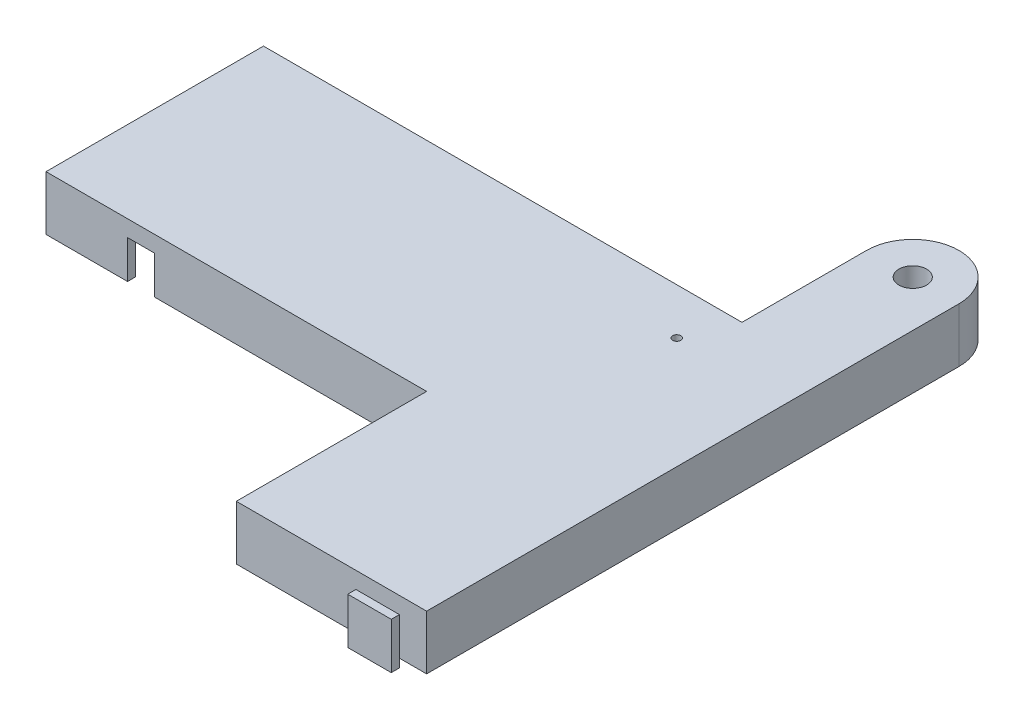
SolidWorks part; units mm, degrees
ref_plane "Front Plane" through (0, 0, 0) normal (0, 0, 1) x (1, 0, 0)
ref_plane "Top Plane" through (0, 0, 0) normal (0, 1, 0) x (1, 0, 0)
ref_plane "Right Plane" through (0, 0, 0) normal (1, 0, 0) x (0, 0, -1)
sketch "CornerSketch1" plane through (0, 0, 0) normal (0, 1, 0) x (1, 0, 0)
  line L0 (210, -70) -> (140, -70)
  line L2 (0, 80) -> (176, 80)
  line L5 (140, -70) -> (140, 0)
  line L6 (140, 0) -> (0, 0)
  line L7 (0, 80) -> (0, 0)
  line L8 (176, 125.825) -> (176, 80)
  line L10 (210, 125.825) -> (210, -70)
  arc A0 (210, 125.825) -> (176, 125.825) centre (193, 125.825) ccw
  dimension "D3" = 34
  dimension "D4" = 70
  dimension "D6" = 45.825
  dimension "D2" = 210
  dimension "D5" = 150
  dimension "D7" = 80
extrude "CornerBoss-Extrude1" add sketch "CornerSketch1" along normal blind 20
shell "Shell1" thickness 3 removed face at (131.5, 0, -36.0813)
sketch "PadSketch2" plane through (0, 17, 0) normal (0, -1, 0) x (1, 0, 0)
  line L0 (210, 70) -> (210, -125.825) construction
  line L1 (176, -80) -> (0, -80) construction
  circle A0 centre (193, -125.825) radius 12
  circle A1 centre (169, -63) radius 5
  dimension "D2" = 10
  dimension "D1" = 24
  dimension "D3" = 41
  dimension "D4" = 17
extrude "PadBoss-Extrude2" add sketch "PadSketch2" along normal blind 10
sketch "StepperRodHoleSketch3" plane through (0, 7, 0) normal (0, -1, 0) x (1, 0, 0)
  circle A0 centre (193, -125.825) radius 5.1
  circle A1 centre (169, -63) radius 1.5
  dimension "D2" = 3
  dimension "D1" = 10.2
extrude "StepperRodHoleCut-Extrude1" cut sketch "StepperRodHoleSketch3" against normal through all
sketch "ThreadedNutMountHolesSketch4" plane through (0, 7, 0) normal (0, -1, 0) x (-1, 0, 0)
  circle A8 centre (-193, 133.825) radius 1
  circle A9 centre (-185, 125.825) radius 1
  circle A10 centre (-201, 125.825) radius 1
  circle A11 centre (-193, 117.825) radius 1
  dimension "D1" = 2
  dimension "D3" = 16
  dimension "D4" = 8
  dimension "D5" = 16
extrude "ThreadedNutMountHolesCut-Extrude2" cut sketch "ThreadedNutMountHolesSketch4" against normal blind 10
sketch "TLPegHoleSketch1" plane through (0, 0, 0) normal (-1, 0, 0) x (0, 0, 1)
  line L1 (-70, 14) -> (-60, 14)
  line L2 (-70, 14) -> (-70, 0)
  line L3 (-70, 0) -> (-60, 0)
  line L4 (-60, 14) -> (-60, 0)
  line L7 (-80, 0) -> (0, 0) construction
  line L8 (-80, 20) -> (-80, 0) construction
  dimension "D2" = 10
  dimension "D1" = 10
  dimension "D3" = 14
extrude "TLPegHoleCut-Extrude1" cut sketch "TLPegHoleSketch1" against normal blind 3
sketch "BottomPegSketch2" plane through (0, 0, 70) normal (0, 0, 1) x (1, 0, 0)
  line L1 (190.1, 13.9) -> (199.9, 13.9)
  line L2 (190.1, 13.9) -> (190.1, 0)
  line L3 (190.1, 0) -> (199.9, 0)
  line L4 (199.9, 13.9) -> (199.9, 0)
  line L6 (210, 20) -> (210, 0) construction
  line L7 (140, 0) -> (210, 0) construction
  dimension "D2" = 13.9
  dimension "D3" = 9.8
  dimension "D1" = 10.1
extrude "BottomPegBoss-Extrude1" add sketch "BottomPegSketch2" along normal blind 3.1
sketch "BottomPegCapSketch3" plane through (0, 0, 73.1) normal (0, 0, 1) x (1, 0, 0)
  line L1 (187.1, 17) -> (203.1, 17)
  line L2 (187.1, 17) -> (187.1, 0)
  line L3 (187.1, 0) -> (203.1, 0)
  line L4 (203.1, 17) -> (203.1, 0)
  line L6 (140, 0) -> (190.1, 0) construction
  line L7 (190.1, 13.9) -> (190.1, 0) construction
  dimension "D1" = 16
  dimension "D3" = 17
  dimension "D2" = 3
extrude "BottomPegCapBoss-Extrude2" add sketch "BottomPegCapSketch3" along normal blind 3
sketch "BedCenterHoleCutSketch1" plane through (0, 0, 0) normal (0, 0, 1) x (1, 0, 0)
  line L0 (0, 0) -> (140, 0) construction
  line L1 (30, 14) -> (40, 14)
  line L2 (30, 14) -> (30, 0)
  line L3 (30, 0) -> (40, 0)
  line L4 (40, 14) -> (40, 0)
  line L5 (140, 20) -> (140, 0) construction
  dimension "D2" = 10
  dimension "D1" = 14
  dimension "D3" = 100
extrude "BedCenterHoleCut-Extrude1" cut sketch "BedCenterHoleCutSketch1" against normal blind 3
equation "\"BedThickness\"= 20mm"
equation "\"BedToBuildPlateStandoffHolesDistanceFromLeftOrRight\"= \"BuildPlateStandoffHolesDistanceFromLeftOrRight\" + \"BedIncreasedByWidth\" / 2'Equals 17"
equation "\"BedToBuildPlateStandoffHolesDistanceFromBack\"= \"BuildPlateStandoffHolesDistanceFromBack\" + \"BedIncreasedByLength\" / 2'Equals 41"
equation "\"BedToBuildPlateStandoffHoleSize\"= 3mm"
equation "\"BedLLongSide\"= \"BedThirdSize\" * 3'Equals 210"
equation "\"BedLShortSide\"= \"BedThirdSize\" * 2'Equals 140"
equation "\"BedIncreasedByWidth\"= 20mm"
equation "\"BedIncreasedByLength\"= 0mm"
equation "\"BedThirdSize\"= 70mm"
equation "\"BedOverlap\"= 20mm"
equation "\"D3@TLPegHoleSketch1\"=\"BedPegHoleHeight\""
equation "\"StandardWallThickness\"= 3mm"
equation "\"D1@CornerBoss-Extrude1\"=\"BedThickness\""
equation "\"D1@TLPegHoleCut-Extrude1\" = \"StandardWallThickness\""
equation "\"D1@BottomPegBoss-Extrude1\"=\"BedPegBoss\""
equation "\"D2@BottomPegCapSketch3\"=\"StandardWallThickness\""
equation "\"D1@BottomPegCapBoss-Extrude2\" = \"StandardWallThickness\""
equation "\"LeadScrewNutPadSize\"= \"LeadScrewNutMountingHoleFlangeDiameter\" + 2mm'Equals 24"
equation "\"BedToBuildPlateStandoffPadSize\"= 10mm"
equation "\"D1@PadSketch2\" = \"LeadScrewNutPadSize\""
equation "\"D2@PadSketch2\" = \"BedToBuildPlateStandoffPadSize\""
equation "\"D3@PadSketch2\"=\"BedToBuildPlateStandoffHolesDistanceFromBack\""
equation "\"D4@PadSketch2\"=\"BedToBuildPlateStandoffHolesDistanceFromLeftOrRight\""
equation "\"D2@StepperRodHoleSketch3\"=\"BedToBuildPlateStandoffHoleSize\""
equation "\"BuildPlateStandoffHolesDistanceFromLeftOrRight\"= 7mm"
equation "\"BuildPlateStandoffHolesDistanceFromBack\"= 41mm"
equation "\"D1@StepperRodHoleSketch3\"=\"LeadScrewNutInnerShaftFlangeDiameter\""
equation "\"BedLWidth\"= \"BedThirdSize\"'Equals 70"
equation "\"D4@CornerSketch1\"=\"BedLWidth\" + \"BedIncreasedByLength\"/2"
equation "\"D2@CornerSketch1\"=\"BedLLongSide\""
equation "\"D7@CornerSketch1\"=\"BedLWidth\" +\"BedOverlap\"/2"
equation "\"DistanceFromBedSideToStepperHole\"= ( \"DistanceBetweenLeftToRightStepperHoles\" - \"BedWidth\" ) / 2'Equals 45.825"
equation "\"RailThickness\"= .125in'Spec"
equation "\"DistanceBetweenLeftToRightStepperHoles\"= \"FrontBackRailLength\" - \"StepperMountingHoleOffsetFromLeftOrRightSide\" * 2 - \"StepperMountingHoleDistance\"'Equals 461.65"
equation "\"BedInnerSquareWidth\"= \"BedThirdSize\" * 3'Equals 210"
equation "\"FrontBackRailLength\"= 510mm"
equation "\"StepperMountingHoleOffsetFromItsSide\"= 5.5mm'Spec"
equation "\"StepperMountingHoleOffsetFromLeftOrRightSide\"= \"StepperMountingHoleOffsetFromItsSide\" + \"RailThickness\""
equation "\"StepperMountingHoleDistance\"= 31mm'Spec"
equation "\"BedWidth\"= \"BedInnerSquareWidth\" + \"BedLWidth\" * 2 + \"BedIncreasedByWidth\"'Equals 370"
equation "\"D6@CornerSketch1\"=\"DistanceFromBedSideToStepperHole\""
equation "\"DistanceFromBedFrontToStepperHole\"= \"LeadScrewNutPadSize\" + 10mm"
equation "\"D3@CornerSketch1\"=\"DistanceFromBedFrontToStepperHole\""
equation "\"D5@CornerSketch1\"=\"BedLShortSide\" +\"BedIncreasedByWidth\"/2"
equation "\"LeadScrewNutInnerShaftFlangeDiameter\"= 10.2mm'Spec"
equation "\"LeadScrewNutMountHoleDiameter\"= 2mm'Spec is 4.1 but smaller for tapping"
equation "\"LeadScrewNutMountingHoleFlangeDiameter\"= 22mm'Spec"
equation "\"LeadScrewNutMountingHoleDistance\"= 16mm'Spec"
equation "\"D3@ThreadedNutMountHolesSketch4\"=\"LeadScrewNutMountingHoleDistance\""
equation "\"D4@ThreadedNutMountHolesSketch4\"=\"LeadScrewNutMountingHoleDistance\"/2"
equation "\"D5@ThreadedNutMountHolesSketch4\"=\"LeadScrewNutMountingHoleDistance\""
equation "\"D2@ThreadedNutMountHolesSketch4\"=\"LeadScrewNutMountingHoleDistance\"/2"
equation "\"D1@ThreadedNutMountHolesSketch4\"=\"LeadScrewNutMountHoleDiameter\""
equation "\"LeadScrewNutPadDepth\"= \"BedThickness\" / 2'Equals 10"
equation "\"D1@ThreadedNutMountHolesCut-Extrude2\"=\"LeadScrewNutPadDepth\""
equation "\"D1@PadBoss-Extrude2\"= \"LeadScrewNutPadDepth\""
equation "\"BedPegHoleWidth\"= 10mm"
equation "\"BedPegHoleHeight\"= \"BedThickness\" - \"StandardWallThickness\" * 2'Equals 14"
equation "\"BedPegWidth\"= \"BedPegHoleWidth\" - .1mm * 2'For easier assembly"
equation "\"BedPegHeight\"= \"BedPegHoleHeight\" - .1mm'For easier assembly"
equation "\"BedTopPegOffsetFromSide\"= 10mm"
equation "\"BedPegBoss\" = \"StandardWallThickness\" + .1mm'For easier assembly"
equation "\"BedPegCapHeight\" = \"BedThickness\" - \"StandardWallThickness\"'Equals 17"
equation "\"BedPegCapWidth\"= \"BedThickness\" / 2 + \"StandardWallThickness\" * 2'Equals 16"
equation "\"D1@TLPegHoleSketch1\"=\"BedTopPegOffsetFromSide\""
equation "\"D2@TLPegHoleSketch1\"=\"BedPegHoleWidth\""
equation "\"D3@BottomPegSketch2\"=\"BedPegWidth\""
equation "\"D2@BottomPegSketch2\"=\"BedPegHeight\""
equation "\"D1@BottomPegCapSketch3\"=\"BedPegCapWidth\""
equation "\"D3@BottomPegCapSketch3\"=\"BedPegCapHeight\""
equation "\"D1@BedCenterHoleCutSketch1\" = \"BedPegHoleHeight\""
equation "\"D2@BedCenterHoleCutSketch1\" = \"BedPegHoleWidth\""
equation "\"D3@BedCenterHoleCutSketch1\" = \"BedInnerSquareWidth\" / 2 - \"BedPegHoleWidth\" / 2"
equation "\"D1@BedCenterHoleCut-Extrude1\"=\"StandardWallThickness\""
